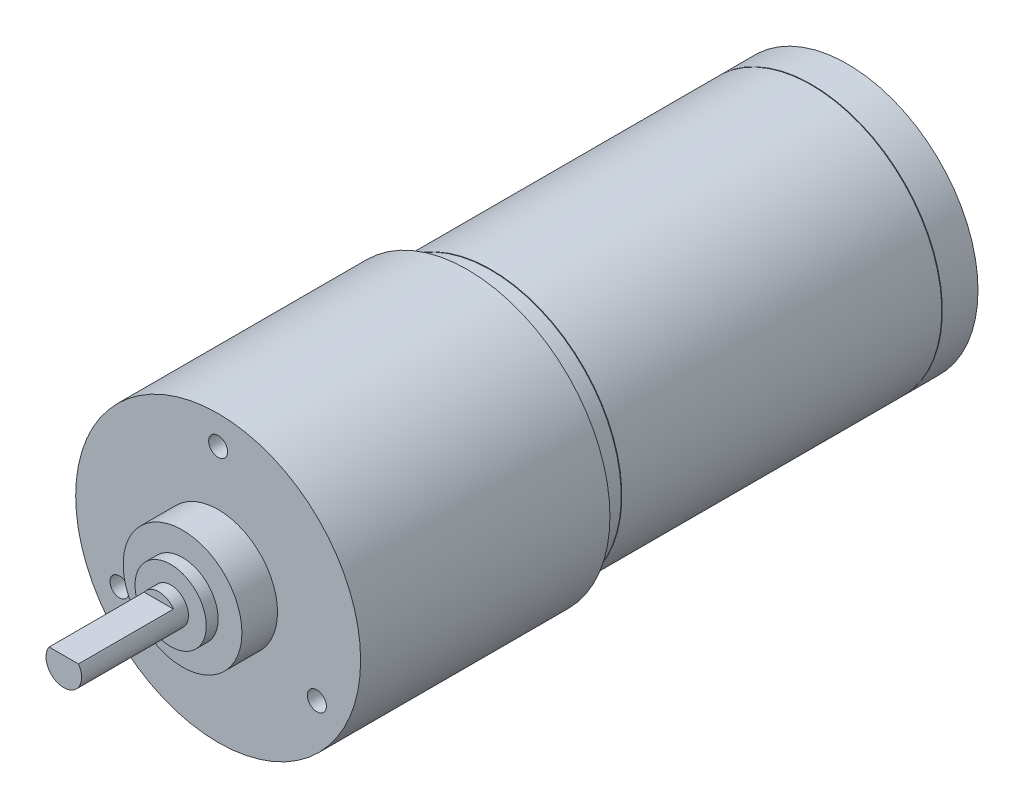
SolidWorks part; units mm, degrees
ref_plane "前视基准面" through (0, 0, 0) normal (0, 0, 1) x (1, 0, 0)
ref_plane "上视基准面" through (0, 0, 0) normal (0, 1, 0) x (1, 0, 0)
ref_plane "右视基准面" through (0, 0, 0) normal (1, 0, 0) x (0, 0, -1)
sketch "草图1" plane through (0, 0, 0) normal (0, 0, 1) x (1, 0, 0)
  circle A0 centre (0, 0) radius 11
  dimension "D1" = 22
extrude "凸台-拉伸1" add sketch "草图1" along normal blind 32
sketch "草图3" plane through (0, 0, 32) normal (0, 0, 1) x (1, 0, 0)
  line L0 (0, 8.5) -> (0, -8.5) construction
  circle A0 centre (0, 0) radius 8.5 construction
  dimension "D1" = 17
hole_wizard "M2 螺纹孔1" positions "3D草图1" profile "草图4" tap size "M2" standard "Gb"
sketch3d "3D草图1"
  point P0 (0, 8.5, 32)
  point P3 (0, -8.5, 32)
sketch "草图4" plane through (0, 8.5, 32) normal (1, 0, 0) x (0, -1, 0)
  line L0 (0, 0) -> (0, 5.6807)
  line L1 (0, 5.6807) -> (0.8, 5.2)
  line L2 (0.8, 5.2) -> (0.8, 0)
  line L5 (0.8, 0) -> (0, 0)
  line L10 (0, 5.6807) -> (-0.8, 5.2) construction
  line L11 (0, -6.35) -> (0, 107.95) construction
  dimension "螺纹孔钻头直径" = 1.6
  dimension "螺纹孔钻头深度" = 5.2
  dimension "导头角度" = 118
cosmetic thread "孔螺蚊线1" parameters "D1"=4, "D2"=2
cosmetic thread "孔螺蚊线2" parameters "D1"=4, "D2"=2
sketch "草图5" plane through (0, 0, 0) normal (0, 0, -1) x (-1, 0, 0)
  circle A0 centre (0, 0) radius 11.8384
  circle A1 centre (0, 0) radius 10.75
  dimension "D1" = 21.5
extrude "切除-拉伸1" cut sketch "草图5" against normal blind 0.05 from offset 3 offset against normal yes
extrude "切除-拉伸2" cut sketch "草图5<2>" against normal blind 0.05 from offset 30 offset against normal yes
sketch "草图5<2>" plane through (0, 0, 0) normal (0, 0, -1) x (-1, 0, 0) same geometry as "草图5"
sketch "草图6" plane through (0, 0, 32) normal (0, 0, 1) x (1, 0, 0)
  circle A0 centre (0, 0) radius 12
  dimension "D1" = 24
extrude "凸台-拉伸2" add sketch "草图6" along normal blind 21
sketch "草图7" plane through (0, 0, 53) normal (0, 0, 1) x (1, 0, 0)
  circle A0 centre (0, 0) radius 5
  dimension "D1" = 10
extrude "凸台-拉伸3" add sketch "草图7" along normal blind 3
sketch "草图8" plane through (0, 0, 53) normal (0, 0, 1) x (1, 0, 0)
  circle A0 centre (0, 0) radius 3
  dimension "D1" = 6
extrude "凸台-拉伸4" add sketch "草图8" along normal blind 4
sketch "草图9" plane through (0, 0, 53) normal (0, 0, 1) x (1, 0, 0)
  circle A0 centre (0, 0) radius 1.5
  dimension "D1" = 3
extrude "凸台-拉伸5" add sketch "草图9" along normal blind 13
sketch "草图10" plane through (0, 0, 66) normal (0, 0, 1) x (1, 0, 0)
  line L0 (-1.5, 0) -> (2.4759, 0) construction
  line L1 (-2.2371, 2.421) -> (2.9057, 2.421)
  line L2 (-2.2371, 2.421) -> (-2.2371, 0.85)
  line L3 (-2.2371, 0.85) -> (2.9057, 0.85)
  line L4 (2.9057, 2.421) -> (2.9057, 0.85)
  circle A0 centre (0, 0) radius 1.5 construction
  circle A1 centre (0, 0) radius 1.5 construction
  dimension "D1" = 0.85
extrude "切除-拉伸3" cut sketch "草图10" against normal blind 8
sketch "草图11" plane through (0, 0, 53) normal (0, 0, 1) x (1, 0, 0)
  circle A0 centre (0, 0) radius 9.6 construction
  point P3 (0, 9.6)
  point P6 (8.3138, -4.8)
  point P7 (-8.3138, -4.8)
  point P8 (0, 0)
  dimension "D1" = 19.2
  dimension "D2" = 3
hole_wizard "M2 螺纹孔2" positions "3D草图2" profile "草图12" tap size "M2" standard "Gb"
sketch3d "3D草图2"
  point P0 (0, 9.6, 53)
  point P3 (8.3138, -4.8, 53)
  point P6 (-8.3138, -4.8, 53)
sketch "草图12" plane through (0, 9.6, 53) normal (1, 0, 0) x (0, -1, 0)
  line L0 (0, 0) -> (0, 5.6807)
  line L1 (0, 5.6807) -> (0.8, 5.2)
  line L2 (0.8, 5.2) -> (0.8, 0)
  line L5 (0.8, 0) -> (0, 0)
  line L10 (0, 5.6807) -> (-0.8, 5.2) construction
  line L11 (0, -6.35) -> (0, 107.95) construction
  dimension "螺纹孔钻头直径" = 1.6
  dimension "螺纹孔钻头深度" = 5.2
  dimension "导头角度" = 118
cosmetic thread "孔螺蚊线3" parameters "D1"=4, "D2"=2
cosmetic thread "孔螺蚊线4" parameters "D1"=4, "D2"=2
cosmetic thread "孔螺蚊线5" parameters "D1"=4, "D2"=2
